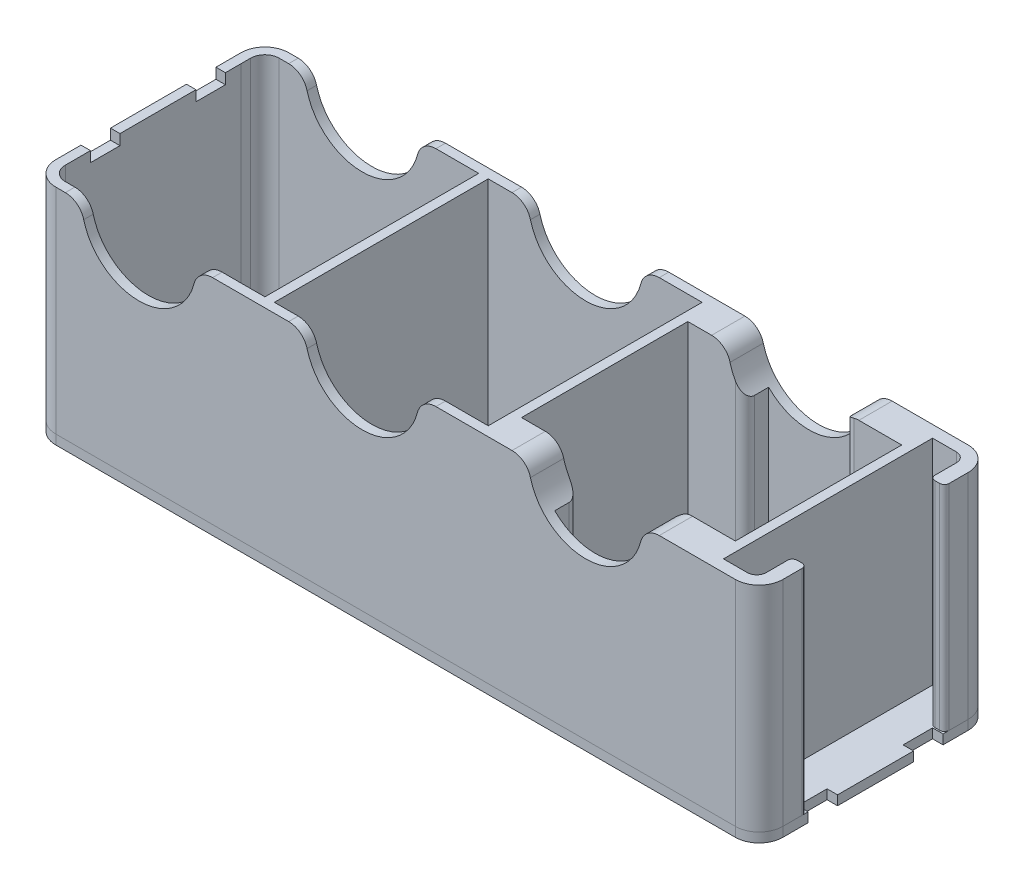
SolidWorks part; units mm, degrees
ref_plane "Спереди" through (0, 0, 0) normal (0, 0, 1) x (1, 0, 0)
ref_plane "Сверху" through (0, 0, 0) normal (0, 1, 0) x (1, 0, 0)
ref_plane "Справа" through (0, 0, 0) normal (1, 0, 0) x (0, 0, -1)
sketch "Эскиз1" plane through (0, 0, 0) normal (0, 1, 0) x (1, 0, 0)
  line L0 (-76.5, 0) -> (-74.5, 0) construction
  line L1 (-71.5, 24.5) -> (71.5, 24.5)
  line L2 (-76.5, 19.5) -> (-76.5, -19.5)
  line L3 (-71.5, -24.5) -> (0, -24.5)
  line L4 (76.5, 19.5) -> (76.5, 15.5)
  line L5 (0, -24.5) -> (0, 24.5) construction
  line L6 (17.5, 0) -> (19.5, 0) construction
  line L7 (-74.5, 0) -> (-29.5, 0) construction
  line L8 (-74.5, 0) -> (-74.5, 17.5)
  line L9 (-29.5, 0) -> (-29.5, 22.5)
  line L10 (-29.5, 22.5) -> (-71.5, 22.5)
  line L11 (-29.5, 24.5) -> (-29.5, 22.5) construction
  line L12 (-29.5, 0) -> (-27.5, 0) construction
  line L13 (-27.5, 0) -> (17.5, 0) construction
  line L14 (19.5, 0) -> (64.5, 0) construction
  line L15 (-27.5, 0) -> (-27.5, 22.5)
  line L16 (-27.5, 22.5) -> (17.5, 22.5)
  line L17 (17.5, 22.5) -> (17.5, 0)
  line L18 (19.5, 0) -> (19.5, 17.5)
  line L19 (31.5, 22.5) -> (52.5, 22.5)
  line L20 (64.5, 17.5) -> (64.5, 0)
  line L21 (75.5, 14.5) -> (74.5, 14.5)
  line L22 (66.5, 0) -> (66.5, 20)
  line L23 (68.5, 22) -> (71.5, 22)
  line L24 (73.5, 20) -> (73.5, 15.5)
  line L25 (64.5, 0) -> (66.5, 0) construction
  line L26 (-74.5, 0) -> (-76.5, 0)
  line L27 (-29.5, 0) -> (-27.5, 0)
  line L28 (17.5, 0) -> (19.5, 0)
  line L29 (64.5, 0) -> (66.5, 0)
  line L30 (0, -24.5) -> (71.5, -24.5)
  line L31 (76.5, -19.5) -> (76.5, 15.5)
  line L32 (-74.5, 19.5045) -> (-74.5, 17.5)
  line L33 (19.5, 17.5) -> (29.5, 17.5)
  line L34 (31.5, 19.5) -> (31.5, 22.5)
  line L35 (64.5, 17.5) -> (54.5, 17.5)
  line L36 (52.5, 19.5) -> (52.5, 22.5)
  line L37 (66.5, 0) -> (66.5, 22)
  line L38 (66.5, 22) -> (68.5, 22)
  line L39 (-27.5, 24.5) -> (-27.5, 22.5) construction
  line L40 (42, 22.5) -> (42, 24.5) construction
  arc A1 (71.5, 24.5) -> (76.5, 19.5) centre (71.5, 19.5) cw
  arc A2 (-71.5, -24.5) -> (-76.5, -19.5) centre (-71.5, -19.5) cw
  arc A3 (-76.5, 19.5) -> (-71.5, 24.5) centre (-71.5, 19.5) cw
  arc A4 (-71.5, 22.5) -> (-74.5, 19.5045) centre (-71.5, 19.5) ccw
  arc A5 (76.5, 15.5) -> (75.5, 14.5) centre (75.5, 15.5) cw
  arc A6 (74.5, 14.5) -> (73.5, 15.5) centre (74.5, 15.5) cw
  arc A7 (76.5, -19.5) -> (71.5, -24.5) centre (71.5, -19.5) cw
  arc A8 (71.5, 22) -> (73.5, 20) centre (71.5, 20) cw
  arc A9 (66.5, 20) -> (68.5, 22) centre (68.5, 20) cw
  arc A10 (54.5, 17.5) -> (52.5, 19.5) centre (54.5, 19.5) cw
  arc A11 (29.5, 17.5) -> (31.5, 19.5) centre (29.5, 19.5) ccw
  point P0 (0, 0)
  point P8 (76.5, 24.5)
  point P12 (-76.5, -24.5)
  point P15 (-76.5, 24.5)
  point P39 (76.5, 14.5)
  point P42 (74.5, 14.5)
  point P49 (74.5, 21.5)
  point P55 (66.5, 0)
  point P59 (52.5, 17.5)
  point P62 (31.5, 17.5)
  dimension "D3" = 5
  dimension "D4" = 5
  dimension "D15" = 1
  dimension "D19" = 2
  dimension "D20" = 2
  dimension "D24" = 2
  dimension "D1" = 153
  dimension "D2" = 49
  dimension "D5" = 2
  dimension "D6" = 45
  dimension "D7" = 2
  dimension "D8" = 2
  dimension "D9" = 45
  dimension "D10" = 2
  dimension "D11" = 45
  dimension "D12" = 2
  dimension "D13" = 7
  dimension "D14" = 2
  dimension "D16" = 12
  dimension "D17" = 5
  dimension "D18" = 12
  dimension "D21" = 22
  dimension "D22" = 2
  dimension "D23" = 2
extrude "Бобышка-Вытянуть2" add sketch "Эскиз1" along normal blind 45 contours A6 L21 A5 L4 A1 L1 A3 L2 L26 L8 L32 A4 L10 L9 L27 L15 L16 L17 L28 L18 L19 L20 L29 L22 region at (0, 0, -22.9505)
extrude "Бобышка-Вытянуть3" add sketch "Эскиз1<6>" against normal blind 2 separate body contours A7 L31 A5 L21 A6 L22 L29 L20 L19 L18 L28 L17 L16 L15 L27 L9 L10 A4 L32 L8 L26 L2 A2 L3 L30 | A6 L21 A5 L4 A1 L1 A3 L2 L26 L8 L32 A4 L10 L9 L27 L15 L16 L17 L28 L18 L19 L20 L29 L22 | L37 A9 L38 region at (0, 0, -22.9505) region at (-0.8843, 0, 1.7411) region at (66.9467, 0, -21.5533)
sketch "Эскиз1<6>" plane through (0, 0, 0) normal (0, 1, 0) x (1, 0, 0) same geometry as "Эскиз1"
mirror "Зеркальное отражение1" about plane through (0, 0, 0) normal (0, 0, 1) of "Бобышка-Вытянуть2"
sketch "Эскиз2" plane through (0, -2, 0) normal (0, -1, 0) x (1, 0, 0)
  line L0 (76.5, 0) -> (74.3, 0) construction
  line L1 (76.5, 19.5) -> (76.5, -19.5) construction
  line L2 (74.3, 0) -> (74.3, 8) construction
  line L4 (74.3, 8) -> (76.5, 8)
  line L5 (74.3, 8) -> (74.3, 14.2)
  line L6 (74.3, 14.2) -> (76.5, 14.2)
  line L7 (76.5, 8) -> (76.5, 14.2)
  dimension "D1" = 6.2
  dimension "D2" = 2.2
  dimension "D3" = 8
extrude "Вырез-Вытянуть1" cut sketch "Эскиз2" against normal blind 2.2 contours L5 L6 L7 L4
mirror "Зеркальное отражение2" about plane through (0, 0, 0) normal (0, 0, 1) of "Вырез-Вытянуть1"
sketch "Эскиз4" plane through (0, 45, 0) normal (0, 1, 0) x (1, 0, 0)
  line L0 (-74.5, 0) -> (-76.5, 0) construction
  line L1 (-74.5, -17.5) -> (-74.5, 17.5) construction
  line L2 (-76.5, 19.5) -> (-76.5, -19.5) construction
  line L3 (-76.5, 0) -> (-76.5, 8) construction
  line L5 (-76.5, 8) -> (-74.5, 8)
  line L6 (-76.5, 8) -> (-76.5, 14.2)
  line L7 (-76.5, 14.2) -> (-74.5, 14.2)
  line L8 (-74.5, 8) -> (-74.5, 14.2)
  dimension "D1" = 6.2
  dimension "D2" = 8
extrude "Вырез-Вытянуть2" cut sketch "Эскиз4" against normal blind 2.2 contours L7 L8 L5 L6
mirror "Зеркальное отражение3" about plane through (0, 0, 0) normal (0, 0, 1) of "Вырез-Вытянуть2"
sketch "Эскиз5" plane through (0, 0, 24.5) normal (0, 0, 1) x (1, 0, 0)
  line L0 (-76.5, 45) -> (-31.5, 45) construction
  line L1 (-71.5, 45) -> (71.5, 45) construction
  line L2 (-31.5, 45) -> (-29.5, 45) construction
  line L3 (-29.5, 45) -> (15.5, 45) construction
  line L4 (15.5, 45) -> (17.5, 45) construction
  line L5 (17.5, 45) -> (62.5, 45) construction
  circle A0 centre (-54, 45) radius 12
  circle A1 centre (-7, 45) radius 12
  circle A2 centre (40, 45) radius 12
  dimension "D6" = 24
  dimension "D7" = 24
  dimension "D8" = 24
  dimension "D1" = 45
  dimension "D2" = 2
  dimension "D3" = 45
  dimension "D4" = 2
  dimension "D5" = 45
extrude "Вырез-Вытянуть3" cut sketch "Эскиз5" against normal through all both and the other way through all
fillet "Скругление1" radius 4 12 edges at (-42, 45, -23.5) (28, 45, -21) (52, 45, -23.5) (52, 45, 23.5) (28, 45, 21) (-19, 45, -23.5) (-19, 45, 23.5) (5, 45, 23.5) (5, 45, -23.5) (-42, 45, 23.5) (-66, 45, 23.5) (-66, 45, -23.5)
